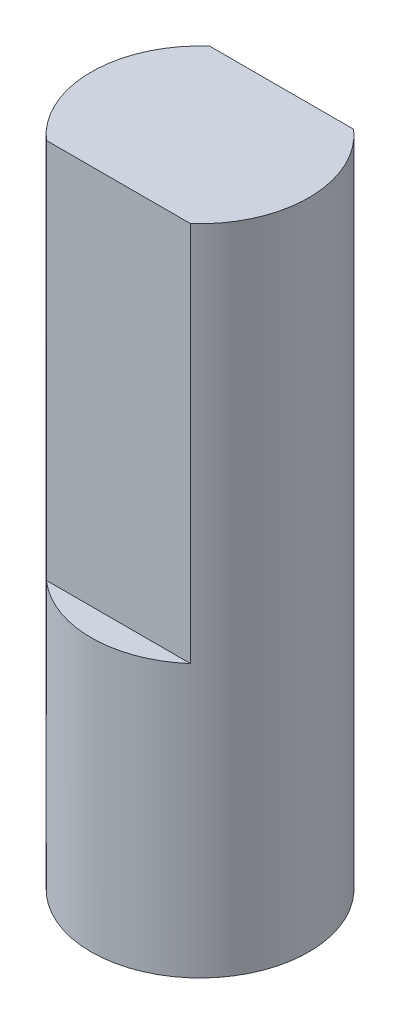
SolidWorks part; units mm, degrees
ref_plane "Alzado" through (0, 0, 0) normal (0, 0, 1) x (1, 0, 0)
ref_plane "Planta" through (0, 0, 0) normal (0, 1, 0) x (1, 0, 0)
ref_plane "Vista lateral" through (0, 0, 0) normal (1, 0, 0) x (0, 0, -1)
sketch "Croquis1" plane through (0, 0, 0) normal (0, 1, 0) x (1, 0, 0)
  circle A2 centre (0, 0) radius 4
  dimension "D1" = 8
extrude "Saliente-Extruir1" add sketch "Croquis1" along normal blind 10
sketch "Croquis2" plane through (0, 10, 0) normal (0, 1, 0) x (1, 0, 0)
  line L1 (-2.6458, -3) -> (2.6458, -3)
  line L3 (-2.6458, 3) -> (2.6458, 3)
  line L5 (-3.4581, -2.0104) -> (3.4581, 2.0104) construction
  line L6 (-3.4581, 2.0104) -> (3.4581, -2.0104) construction
  arc A0 (2.6458, -3) -> (2.6458, 3) centre (0, 0) ccw
  arc A1 (-2.6458, 3) -> (-2.6458, -3) centre (0, 0) ccw
extrude "Saliente-Extruir2" add sketch "Croquis2" along normal blind 14
